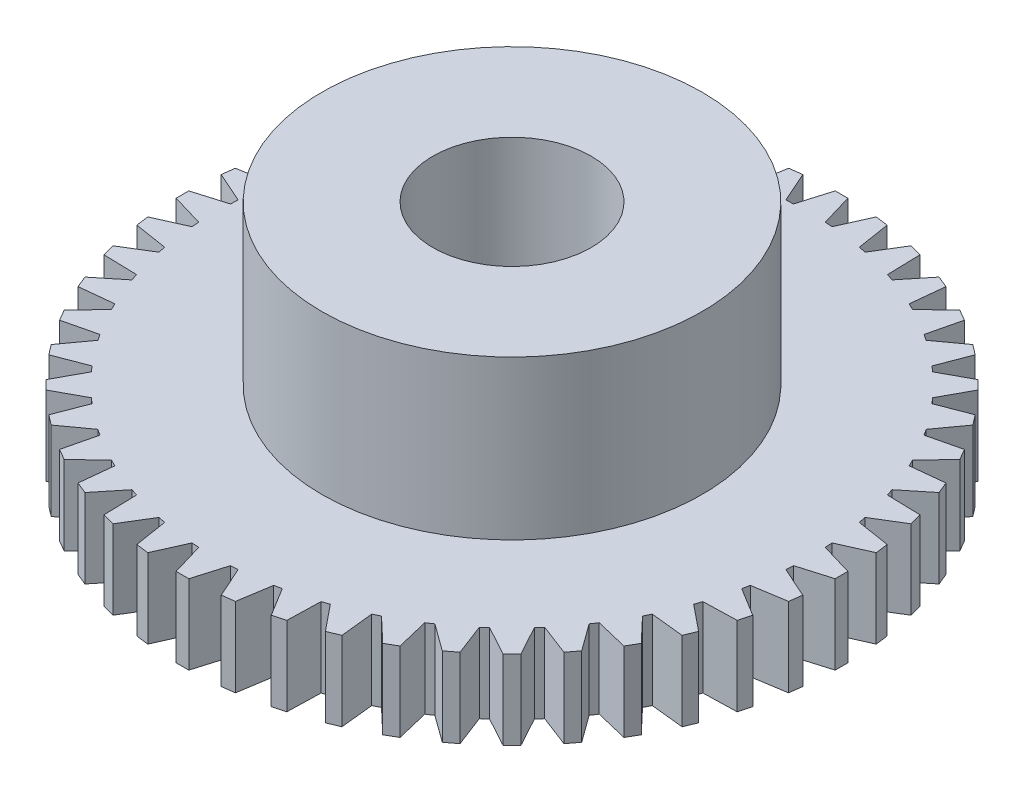
SolidWorks part; units mm, degrees
ref_plane "Front Plane" through (0, 0, 0) normal (0, 0, 1) x (1, 0, 0)
ref_plane "Top Plane" through (0, 0, 0) normal (0, 1, 0) x (1, 0, 0)
ref_plane "Right Plane" through (0, 0, 0) normal (1, 0, 0) x (0, 0, -1)
sketch "Sketch1" plane through (0, 0, 0) normal (0, 1, 0) x (1, 0, 0)
  circle A0 centre (0, 0) radius 3.175
  circle A1 centre (0, 0) radius 7.62
  dimension "D1" = 6.35
  dimension "D2" = 15.24
extrude "Boss-Extrude1" add sketch "Sketch1" along normal blind 9.525 contours A1 A0 region at (-7.4045, 0, 0)
sketch "Sketch2" plane through (0, 0, 0) normal (0, 1, 0) x (1, 0, 0)
  line L0 (0, 0) -> (0, 11.938) construction
  line L1 (-0.635, 11.9211) -> (0.635, 11.9211)
  line L2 (0, 11.938) -> (0, 13.208) construction
  line L3 (-0.254, 13.208) -> (0.254, 13.208)
  line L4 (-0.254, 13.208) -> (-0.635, 11.9211)
  line L5 (0.254, 13.208) -> (0.635, 11.9211)
  circle A0 centre (0, 0) radius 11.938
  point P11 (0, 13.208)
  dimension "D1" = 23.876
  dimension "D2" = 1.27
  dimension "D3" = 1.27
  dimension "D4" = 0.508
extrude "Boss-Extrude2" add sketch "Sketch2" along normal blind 3.175 contours L1 A0 region at (0, 0, 0.0004)
extrude "Boss-Extrude3" add sketch "Sketch2<3>" along normal blind 3.175 contours L5 L1 L4 L3
sketch "Sketch2<3>" plane through (0, 0, 0) normal (0, 1, 0) x (1, 0, 0) same geometry as "Sketch2"
pattern_circular "CirPattern1" count 48 over 360 about axis through (0, 9.525, 0) along (0, -1, 0) of "Boss-Extrude3" reverse direction yes
equation "\"Number_Teeth\"= 48"
equation "\"Diametral_Pitch\"= 48"
equation "\"Pitch_Diameter\"= \"Number_Teeth\" * \"1_inch\" / \"Diametral_Pitch\""
equation "\"Tooth_Height\"= .05in"
equation "\"Addendum\"= \"Tooth_Height\" * .4"
equation "\"Dedendum\"= \"Tooth_Height\" * .6"
equation "\"D1@Sketch2\"=\"Pitch_Diameter\"-(2*\"Dedendum\")"
equation "\"D3@Sketch2\"=\"Tooth_Height\""
equation "\"1_inch\"= 1in"
equation "\"D1@CirPattern1\"=\"Number_Teeth\""
